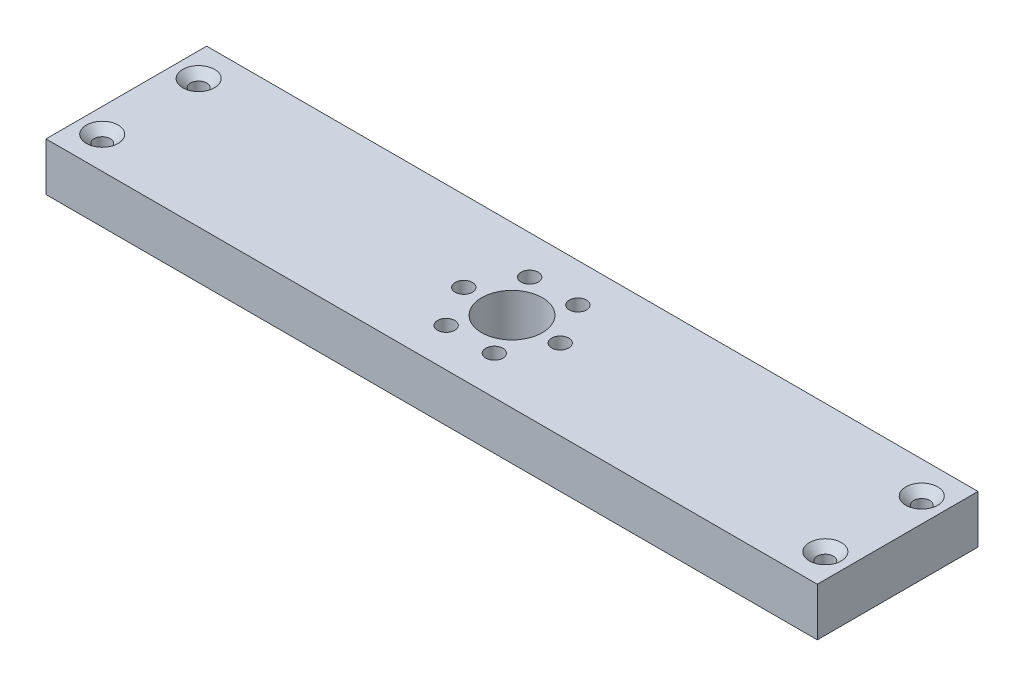
SolidWorks part; units mm, degrees
ref_plane "Front Plane" through (0, 0, 0) normal (0, 0, 1) x (1, 0, 0)
ref_plane "Top Plane" through (0, 0, 0) normal (0, 1, 0) x (1, 0, 0)
ref_plane "Right Plane" through (0, 0, 0) normal (1, 0, 0) x (0, 0, -1)
sketch "Sketch1" plane through (0, 0, 0) normal (0, 1, 0) x (1, 0, 0)
  line L1 (-76.2, -15.875) -> (76.2, -15.875)
  line L2 (-76.2, -15.875) -> (-76.2, 15.875)
  line L3 (-76.2, 15.875) -> (76.2, 15.875)
  line L4 (76.2, -15.875) -> (76.2, 15.875)
  line L5 (-76.2, -15.875) -> (76.2, 15.875) construction
  line L6 (-76.2, 15.875) -> (76.2, -15.875) construction
  point P0 (0, 0)
  dimension "D1" = 152.4
  dimension "D2" = 31.75
extrude "Boss-Extrude1" add sketch "Sketch1" along normal mid plane 9.525
sketch "Sketch3" plane through (0, 4.7625, 0) normal (0, 1, 0) x (1, 0, 0)
  line L0 (71.4375, -9.525) -> (-71.4375, -9.525) construction
  line L1 (-76.2, -15.875) -> (76.2, -15.875) construction
  point P0 (-71.4375, 9.525)
  point P1 (-71.4375, -9.525)
  point P3 (71.4375, -9.525)
  point P5 (71.4375, 9.525)
  point P6 (0, -9.525)
  point P12 (0, -15.875)
hole_wizard "CSK for M3 Flat Head Machine Screw1" positions "Sketch4" profile "Sketch6" countersink size "M3" standard "ANSI Metric" end condition through all
sketch "Sketch4" plane through (0, 4.7625, 0) normal (0, 1, 0) x (1, 0, 0)
  point P0 (-71.4375, 9.525)
  point P3 (-71.4375, -9.525)
  point P8 (71.4375, 9.525)
  point P14 (71.4375, -9.525)
sketch "Sketch6" plane through (-71.4375, 4.7625, -9.525) normal (1, 0, 0) x (0, 0, 1)
  line L0 (0, 0) -> (0, 9.525)
  line L1 (0, 9.525) -> (1.6, 9.525)
  line L2 (1.6, 9.525) -> (1.6, 1.55)
  line L3 (1.6, 1.55) -> (3.15, 0)
  line L5 (3.15, 0) -> (0, 0)
  line L6 (-1.6, 1.55) -> (-3.15, 0) construction
  line L11 (0, -6.35) -> (0, 107.95) construction
  dimension "Thru Hole Dia." = 3.2
  dimension "Thru Hole Depth" = 9.525
  dimension "Near C'Sink Dia." = 6.3
  dimension "Near C'Sink Angle" = 90
sketch "Sketch7" plane through (0, -4.7625, 0) normal (0, -1, 0) x (1, 0, 0)
  point P0 (0, 0)
hole_wizard "Ø12.0mm Dowel Hole1" positions "Sketch8" profile "Sketch9" hole size "Ø12.0" standard "ANSI Metric" end condition through all
sketch "Sketch8" plane through (0, -4.7625, 0) normal (0, -1, 0) x (-1, 0, 0)
  point P0 (0, 0)
sketch "Sketch9" plane through (0, -4.7625, 0) normal (1, 0, 0) x (0, 0, -1)
  line L0 (0, 0) -> (0, 9.525)
  line L1 (0, 9.525) -> (6, 9.525)
  line L2 (6, 9.525) -> (6, 0)
  line L5 (6, 0) -> (0, 0)
  line L11 (0, -6.35) -> (0, 107.95) construction
  dimension "Thru Hole Dia." = 12
  dimension "Thru Hole Depth" = 9.525
sketch "Sketch11" plane through (0, -4.7625, 0) normal (0, -1, 0) x (1, 0, 0)
  point P9 (-4.7625, 8.2489)
  point P11 (4.7625, 8.2489)
  point P13 (9.525, 0)
  point P15 (-9.525, 0)
  point P17 (-4.7625, -8.2489)
  point P19 (4.7625, -8.2489)
hole_wizard "CBORE for M3 SHCS1" positions "Sketch12" profile "Sketch14" counterbore size "M3" standard "ANSI Metric" end condition through all
sketch "Sketch12" plane through (0, -4.7625, 0) normal (0, -1, 0) x (-1, 0, 0)
  point P19 (4.7625, -8.2489)
  point P22 (9.525, 0)
  point P25 (4.7625, 8.2489)
  point P28 (-4.7625, 8.2489)
  point P31 (-9.525, 0)
  point P34 (-4.7625, -8.2489)
sketch "Sketch14" plane through (-4.7625, -4.7625, 8.2489) normal (1, 0, 0) x (0, 0, -1)
  line L0 (0, 0) -> (0, 9.525)
  line L1 (0, 9.525) -> (1.7, 9.525)
  line L3 (1.7, 9.525) -> (1.7, 2)
  line L4 (1.7, 2) -> (2.25, 2)
  line L5 (2.25, 2) -> (2.25, 0)
  line L7 (2.25, 0) -> (0, 0)
  line L11 (0, -6.35) -> (0, 107.95) construction
  dimension "Thru Hole Dia." = 3.4
  dimension "Thru Hole Depth" = 9.525
  dimension "C'Bore Dia." = 4.5
  dimension "C'Bore Depth" = 2
